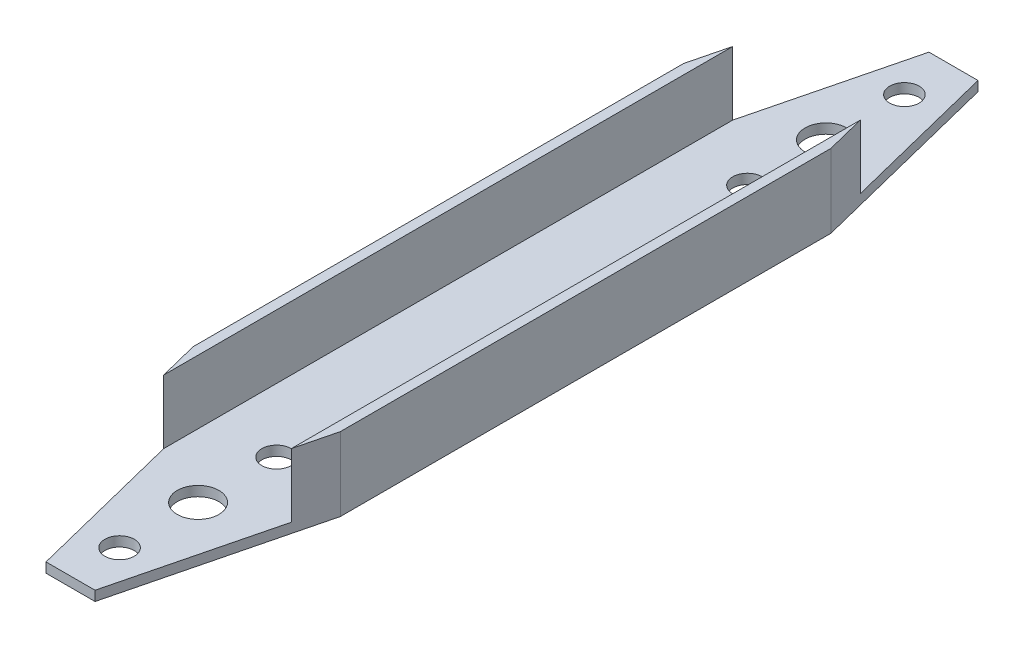
SolidWorks part; units mm, degrees
material "1060 slitina"
ref_plane "Front" through (0, 0, 0) normal (0, 0, 1) x (1, 0, 0)
ref_plane "Top" through (0, 0, 0) normal (0, 1, 0) x (1, 0, 0)
ref_plane "Right" through (0, 0, 0) normal (1, 0, 0) x (0, 0, -1)
sketch "Skica1" plane through (0, 0, 0) normal (0, 0, 1) x (1, 0, 0)
  line L0 (28, 15) -> (30, 15)
  line L1 (0, 0) -> (30, 0)
  line L2 (0, 0) -> (0, 15)
  line L3 (0, 15) -> (2, 15)
  line L4 (30, 0) -> (30, 15)
  line L6 (2, 15) -> (2, 2)
  line L7 (2, 2) -> (28, 2)
  line L8 (28, 15) -> (28, 2)
  dimension "D1" = 30
  dimension "D2" = 15
  dimension "D3" = 2
  dimension "D4" = 2
  dimension "D5" = 2
extrude "Přidat vysunutím1" add sketch "Skica1" along normal blind 180
sketch "Skica2" plane through (0, 2, 0) normal (0, 1, 0) x (1, 0, 0)
  line L0 (15, -180) -> (15, 0) construction
  line L1 (28, -180) -> (2, -180) construction
  line L2 (28, 0) -> (2, 0) construction
  line L3 (15.71, -154) -> (50015.71, -154) construction
  line L5 (2, -90) -> (50002, -90) construction
  line L6 (2, -180) -> (2, 0) construction
  line L7 (28, -180) -> (28, 0) construction
  circle A0 centre (15, -170) radius 3
  circle A1 centre (15, -154) radius 4.25
  circle A2 centre (15, -138) radius 3
  circle A3 centre (15, -42) radius 3
  circle A4 centre (15, -26) radius 4.25
  circle A5 centre (15, -10) radius 3
  point P20 (2, -90)
  point P23 (28, -90)
  dimension "D1" = 26
  dimension "D2" = 8.5
  dimension "D3" = 6
  dimension "D4" = 16
extrude "Odebrat vysunutím1" cut sketch "Skica2" against normal up to next
sketch "Skica3" plane through (0, 0, 0) normal (0, -1, 0) x (1, 0, 0)
  line L0 (15, 180) -> (15, -49820) construction
  line L3 (0, 0) -> (30, 0) construction
  line L4 (0, 90) -> (50000, 90) construction
  line L5 (30, 180) -> (30, 0) construction
  line L6 (0, 180) -> (0, 0) construction
  line L7 (30, 180) -> (20, 180)
  line L8 (30, 140) -> (30, 180)
  line L9 (20, 180) -> (30, 140)
  line L10 (0, 180) -> (30, 180) construction
  line L11 (0, 0) -> (10, 0)
  line L12 (0, 40) -> (0, 0)
  line L13 (10, 180) -> (0, 140)
  line L14 (0, 140) -> (0, 180)
  line L15 (0, 180) -> (10, 180)
  line L16 (10, 0) -> (0, 40)
  line L17 (20, 0) -> (30, 40)
  line L18 (30, 40) -> (30, 0)
  line L19 (30, 0) -> (20, 0)
  point P2 (15, 180)
  point P5 (15, 0)
  point P9 (0, 90)
  point P15 (30, 90)
  dimension "D6" = 10
  dimension "D7" = 40
extrude "Odebrat vysunutím2" cut sketch "Skica3" against normal up to surface (15 mm away) up to face at (29, 15, 90)
fillet "Zaoblit1" [suppressed] radius 3
